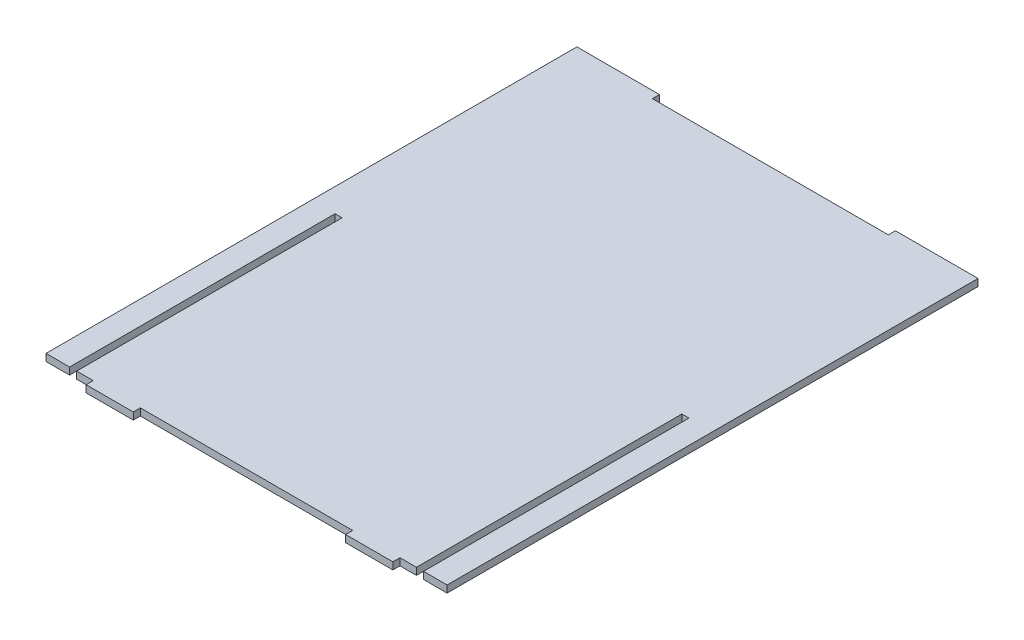
SolidWorks part; units mm, degrees
ref_plane "Front Plane" through (0, 0, 0) normal (0, 0, 1) x (1, 0, 0)
ref_plane "Top Plane" through (0, 0, 0) normal (0, 1, 0) x (1, 0, 0)
ref_plane "Right Plane" through (0, 0, 0) normal (1, 0, 0) x (0, 0, -1)
sketch "Sketch1" plane through (0, 0, 0) normal (0, 1, 0) x (1, 0, 0)
  line L0 (300, 0) -> (300, -6)
  line L2 (0, 0) -> (0, 450)
  line L3 (0, 450) -> (340, 450)
  line L4 (340, 0) -> (340, 450)
  line L5 (300, -6) -> (260, -6)
  line L6 (260, -6) -> (260, 0)
  line L7 (40, 0) -> (40, -6)
  line L8 (40, -6) -> (80, -6)
  line L9 (80, -6) -> (80, 0)
  line L10 (40, 0) -> (0, 0)
  line L11 (80, 0) -> (260, 0)
  line L12 (300, 0) -> (340, 0)
  point P11 (80, -3)
  dimension "D1" = 340
  dimension "D2" = 450
  dimension "D3" = 40
  dimension "D4" = 6
  dimension "D5" = 40
  dimension "D6" = 180
extrude "Boss-Extrude1" add sketch "Sketch1" along normal blind 6
sketch "Sketch2" plane through (0, 6, 0) normal (0, 1, 0) x (1, 0, 0)
  line L1 (20, 0) -> (26, 0)
  line L2 (20, 0) -> (20, 225)
  line L3 (20, 225) -> (26, 225)
  line L4 (26, 0) -> (26, 225)
  line L5 (0, 450) -> (0, 0) construction
  line L6 (0, 0) -> (40, 0) construction
  line L7 (0, 0) -> (40, 0) construction
  dimension "D1" = 225
  dimension "D2" = 6
  dimension "D3" = 20
extrude "Cut-Extrude1" cut sketch "Sketch2" against normal blind 6
pattern_linear "LPattern1" count 2 spacing 294 along (1, 0, 0) of "Cut-Extrude1"
sketch "Sketch3" plane through (0, 6, 0) normal (0, 1, 0) x (1, 0, 0)
  line L3 (340, 450) -> (0, 450) construction
  line L4 (70, 450) -> (270, 450)
  line L5 (70, 450) -> (70, 444)
  line L6 (70, 444) -> (270, 444)
  line L7 (270, 450) -> (270, 444)
  dimension "D1" = 200
  dimension "D5" = 6
extrude "Cut-Extrude2" cut sketch "Sketch3" against normal blind 6
